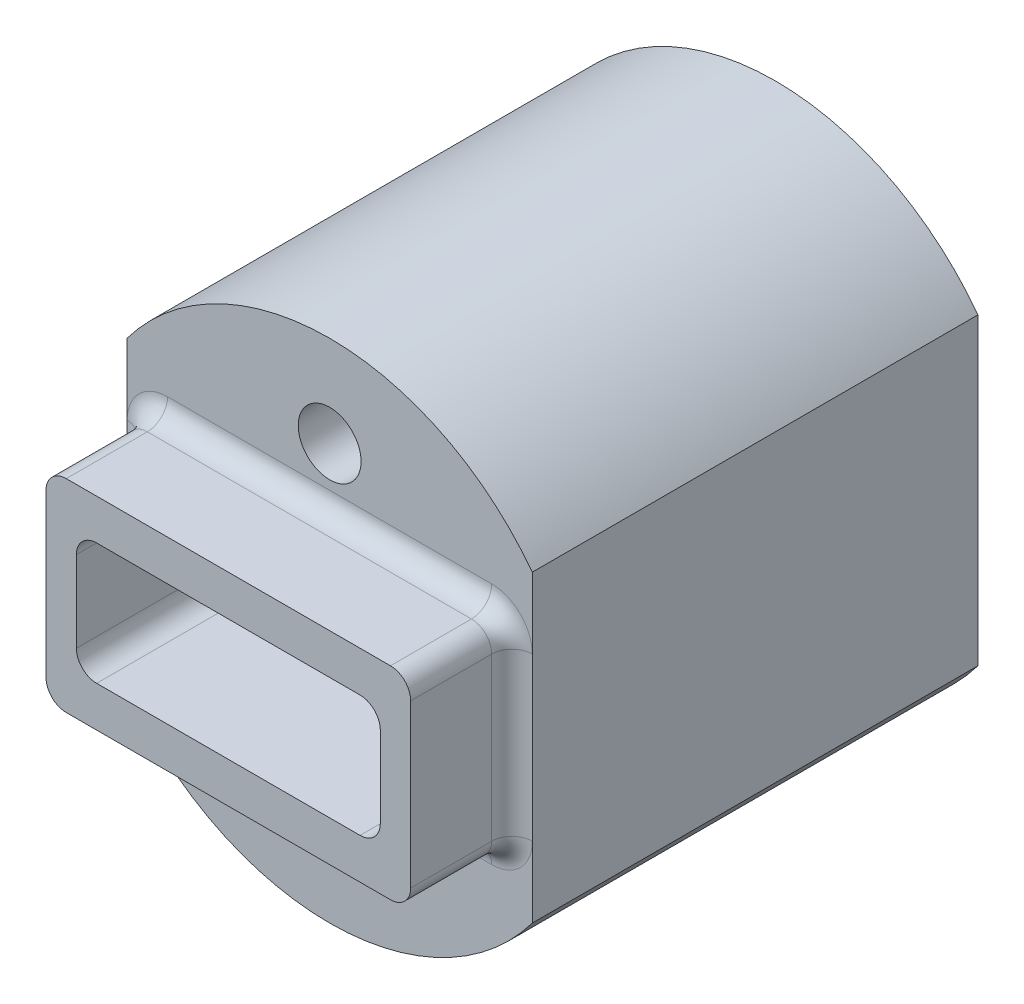
SolidWorks part; units mm, degrees
ref_plane "Ebene vorne" through (0, 0, 0) normal (0, 0, 1) x (1, 0, 0)
ref_plane "Ebene oben" through (0, 0, 0) normal (0, 1, 0) x (1, 0, 0)
ref_plane "Ebene rechts" through (0, 0, 0) normal (1, 0, 0) x (0, 0, -1)
sketch "Skizze1" plane through (0, 0, 0) normal (0, 0, 1) x (1, 0, 0)
  line L0 (0, 26.6232) -> (0, -18.9292) construction
  line L1 (-23.6459, 0) -> (19.5794, 0) construction
  circle A0 centre (0, 0) radius 12.5
  circle A1 centre (0, 8) radius 1.55
  circle A2 centre (0, -8) radius 1.55
  dimension "D1" = 25
  dimension "D2" = 3.1
  dimension "D3" = 16
extrude "Aufsatz-Linear austragen1" add sketch "Skizze1" along normal blind 7.5 and the other way blind 14.5
sketch "Skizze2" plane through (0, 0, -14.5) normal (0, 0, -1) x (-1, 0, 0)
  line L0 (-20.9915, 0) -> (20.1572, 0) construction
  line L1 (0, 18.5911) -> (0, -18.5544) construction
  line L2 (-9, -4) -> (-9, 4)
  line L3 (-8, 5) -> (8, 5)
  line L4 (-8, -5) -> (8, -5)
  line L5 (9, -4) -> (9, 4)
  arc A0 (-8, 5) -> (-9, 4) centre (-8, 4) ccw
  arc A1 (-8, -5) -> (-9, -4) centre (-8, -4) cw
  arc A2 (8, -5) -> (9, -4) centre (8, -4) ccw
  arc A3 (8, 5) -> (9, 4) centre (8, 4) cw
  point P13 (0, 5)
  point P14 (-9, 0)
  point P20 (9, 0)
  point P21 (0, -5)
  dimension "D1" = 1
  dimension "D2" = 10
  dimension "D3" = 18
extrude "Schnitt-Linear austragen1" cut sketch "Skizze2" against normal blind 4.5
sketch "Skizze3" plane through (0, 0, 7.5) normal (0, 0, 1) x (1, 0, 0)
  line L0 (18.7113, 0) -> (-15.5181, 0) construction
  line L1 (0, 15.8588) -> (0, -16.495) construction
  line L2 (-8, 5) -> (8, 5)
  line L3 (9, 4) -> (9, -4)
  line L4 (-8, -5) -> (8, -5)
  line L5 (-9, 4) -> (-9, -4)
  arc A0 (8, 5) -> (9, 4) centre (8, 4) cw
  arc A1 (8, -5) -> (9, -4) centre (8, -4) ccw
  arc A2 (-8, -5) -> (-9, -4) centre (-8, -4) cw
  arc A3 (-8, 5) -> (-9, 4) centre (-8, 4) ccw
  point P8 (0, 5)
  point P13 (9, 0)
  point P20 (-9, 0)
  point P21 (0, -5)
  dimension "D1" = 1
  dimension "D2" = 18
  dimension "D3" = 10
extrude "Aufsatz-Linear austragen2" add sketch "Skizze3" along normal blind 5
sketch "Skizze4" plane through (0, 0, 0) normal (0, 0, 1) x (1, 0, 0)
  line L0 (23.0396, 0) -> (-15.6217, 0) construction
  line L1 (0, -18.7774) -> (0, 16.1377) construction
  line L2 (-6.5, -3) -> (6.5, -3)
  line L3 (7.5, -2) -> (7.5, 2)
  line L4 (-7.5, -2) -> (-7.5, 2)
  line L5 (-6.5, 3) -> (6.5, 3)
  arc A0 (6.5, -3) -> (7.5, -2) centre (6.5, -2) ccw
  arc A1 (-6.5, -3) -> (-7.5, -2) centre (-6.5, -2) cw
  arc A2 (-6.5, 3) -> (-7.5, 2) centre (-6.5, 2) ccw
  arc A3 (6.5, 3) -> (7.5, 2) centre (6.5, 2) cw
  point P13 (7.5, 0)
  point P14 (0, -3)
  point P20 (0, 3)
  point P21 (-7.5, 0)
  dimension "D1" = 1
  dimension "D2" = 15
  dimension "D3" = 6
extrude "Schnitt-Linear austragen4" cut sketch "Skizze4" against normal through all and the other way through all
ref_axis "Achse1" through (0, 0, 13.475) along (0, 0, -1)
sketch "Skizze5" plane through (0, 0, 0) normal (0, 0, 1) x (1, 0, 0)
  line L0 (0, 18.6124) -> (0, -19.0354) construction
  line L1 (18.2952, 0) -> (-19.1412, 0) construction
  line L2 (10, 15) -> (10, -15)
  line L3 (10, 15) -> (-10, 15)
  line L4 (10, -15) -> (-10, -15)
  line L5 (-10, 15) -> (-10, -15)
  point P9 (10, 0)
  point P10 (-10, 0)
  point P12 (0, -15)
  point P13 (0, 15)
  dimension "D1" = 20
  dimension "D2" = 30
extrude "Schnitt-Linear austragen5" cut sketch "Skizze5" against normal through all and the other way blind 10 flip side to cut
fillet "Verrundung1" radius 1.2 8 edges at (-8.7071, 4.7071, -14.5) (-8.7071, -4.7071, -14.5) (0, -5, -14.5) (8.7071, -4.7071, -14.5) (8.7071, 4.7071, -14.5) (0, 5, -14.5) (-9, 0, -14.5) (9, 0, -14.5)
fillet "Verrundung2" radius 1 8 edges at (8.7071, 4.7071, 7.5) (9, 0, 7.5) (8.7071, -4.7071, 7.5) (0, -5, 7.5) (-8.7071, -4.7071, 7.5) (-9, 0, 7.5) (-8.7071, 4.7071, 7.5) (0, 5, 7.5)
